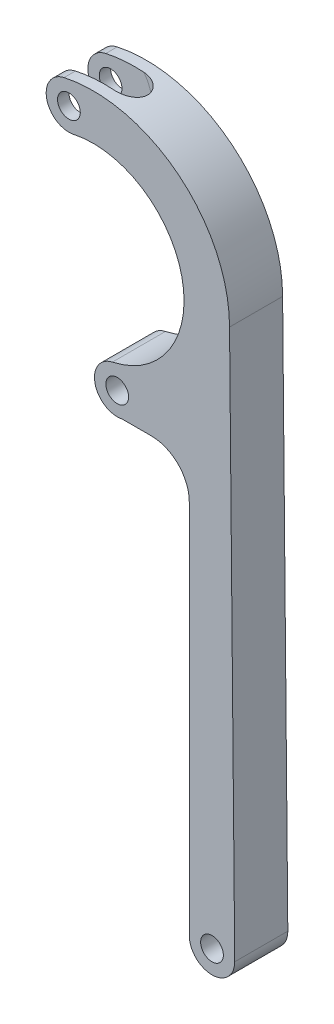
SolidWorks part; units mm, degrees
ref_plane "Alzado" through (0, 0, 0) normal (0, 0, 1) x (1, 0, 0)
ref_plane "Planta" through (0, 0, 0) normal (0, 1, 0) x (1, 0, 0)
ref_plane "Vista lateral" through (0, 0, 0) normal (1, 0, 0) x (0, 0, -1)
sketch "Croquis1" plane through (0, 0, 0) normal (0, 0, 1) x (1, 0, 0)
  line L0 (0, 115) -> (0, 0) construction
  line L1 (0, 115) -> (-25, 115) construction
  line L2 (0, 0) -> (-25, 115) construction
  line L3 (-25, 115) -> (-37.7458, 173.6306) construction
  line L4 (4.6271, 144.3153) -> (6, 0)
  line L5 (-6, 0) -> (-6, 99.1369)
  line L6 (-16, 109.1369) -> (-23.7254, 109.1369)
  circle A0 centre (0, 0) radius 6
  circle A1 centre (0, 0) radius 3
  circle A2 centre (-25, 115) radius 6
  circle A3 centre (-25, 115) radius 3
  circle A4 centre (-37.7458, 173.6306) radius 6
  circle A5 centre (-37.7458, 173.6306) radius 3
  arc A6 (-26.2746, 120.8631) -> (-36.4712, 167.7675) centre (-31.3729, 144.3153) ccw
  arc A7 (-23.7254, 109.1369) -> (-39.0204, 179.4936) centre (-31.3729, 144.3153) ccw
  arc A8 (-16, 109.1369) -> (-6, 99.1369) centre (-16, 99.1369) cw
  dimension "D1" = 6
  dimension "D2" = 12
  dimension "D3" = 12
  dimension "D4" = 6
  dimension "D7" = 12
  dimension "D8" = 6
  dimension "D10" = 10
  dimension "D5" = 25
  dimension "D6" = 115
  dimension "D9" = 60
extrude "Saliente-Extruir1" add sketch "Croquis1" along normal blind 14 contours A7 A4 A6 A2 | A4 A5 | A2 A3 | L6 A8 L5 A0 L4 A7 | L4 A0 A1 region at (-0.774, 67.5957, 0) region at (-3.9935, 122.2484, 0) region at (5.8298, 0.0555, 0) region at (-30.6972, 113.7615, 0) region at (-34.0871, 178.17, 0)
sketch "Croquis3" plane through (0, 0, 14) normal (0, 0, 1) x (1, 0, 0)
  circle A0 centre (-37.7458, 173.6306) radius 15
  dimension "D1" = 30
extrude "Cortar-Extruir1" cut sketch "Croquis3" against normal blind 8 from offset 3 offset against normal yes
fillet "Redondeo1" radius 4 2 edges at (-22.7483, 173.3548, 11) (-22.7483, 173.3548, 3)
